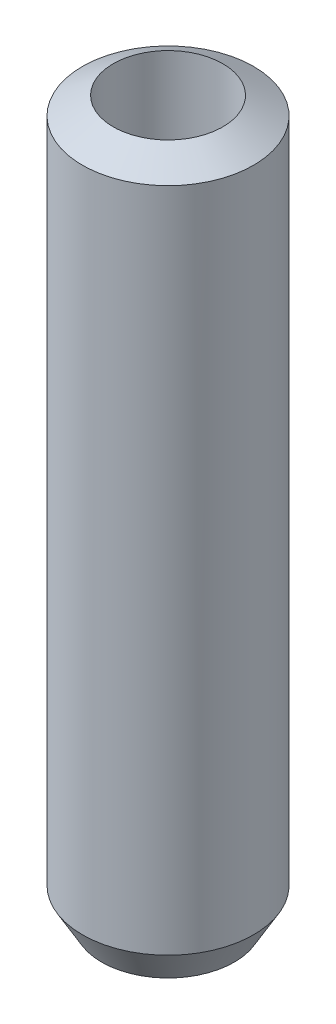
SolidWorks part; units mm, degrees
ref_plane "Front Plane" through (0, 0, 0) normal (0, 0, 1) x (1, 0, 0)
ref_plane "Top Plane" through (0, 0, 0) normal (0, 1, 0) x (1, 0, 0)
ref_plane "Right Plane" through (0, 0, 0) normal (1, 0, 0) x (0, 0, -1)
sketch "Sketch1" plane through (0, 0, 0) normal (0, 1, 0) x (1, 0, 0)
  circle A0 centre (0, 0) radius 25
  dimension "SHAFT_OD" = 50
extrude "Boss-Extrude1" add sketch "Sketch1" along normal blind 209.9859
sketch "Sketch2" plane through (0, 0, 0) normal (0, 1, 0) x (1, 0, 0)
  circle A0 centre (0, 0) radius 15.9978
  dimension "BORE_D" = 31.9955
extrude "Cut-Extrude1" cut sketch "Sketch2" along normal through all
chamfer "Chamfer1" distance 5.6229 angle 60 2 edges at (0, 209.9859, 25) (0, 0, 25) first distance on face at (0, 209.9859, 25) first distance on face at (0, 0, 15.9978)
